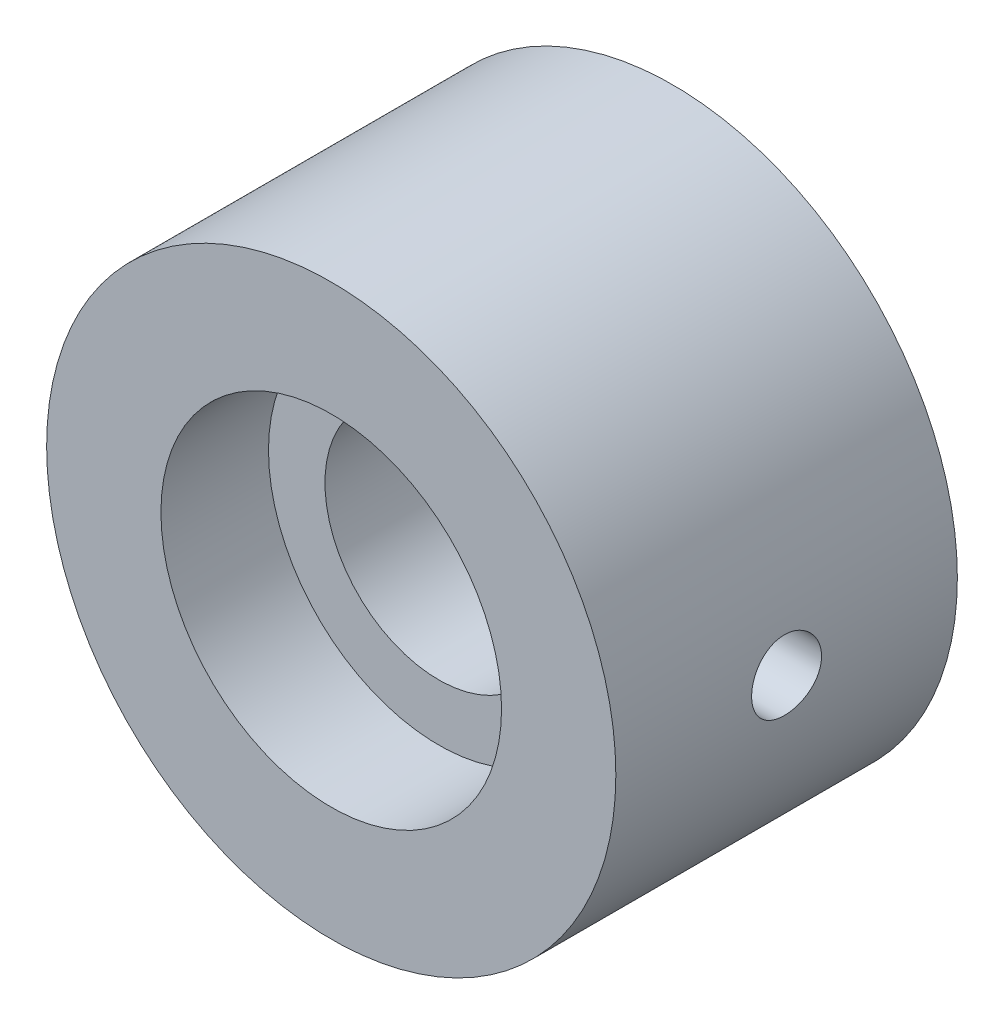
SolidWorks part; units mm, degrees
material "PLA"
ref_plane "Front Plane" through (0, 0, 0) normal (0, 0, 1) x (1, 0, 0)
ref_plane "Top Plane" through (0, 0, 0) normal (0, 1, 0) x (1, 0, 0)
ref_plane "Right Plane" through (0, 0, 0) normal (1, 0, 0) x (0, 0, -1)
sketch "Sketch1" plane through (0, 0, 0) normal (0, 0, 1) x (1, 0, 0)
  circle A0 centre (0, 0) radius 9.5
  circle A1 centre (0, 0) radius 15.875
  circle A2 centre (0, 0) radius 6.35
  dimension "D1" = 19
  dimension "D2" = 31.75
  dimension "D3" = 12.7
extrude "Boss-Extrude1" add sketch "Sketch1" along normal blind 6 contours A1 A0 region at (-15.426, 0, 0)
extrude "Boss-Extrude2" add sketch "Sketch1<3>" against normal blind 13.05 contours A0 A2 | A1 A0 region at (-9.2313, 0, 0) region at (-15.426, 0, 0)
sketch "Sketch1<3>" plane through (0, 0, 0) normal (0, 0, 1) x (1, 0, 0) same geometry as "Sketch1"
sketch "Sketch3" plane through (0, 0, -13.05) normal (0, 0, -1) x (-1, 0, 0)
  line L0 (0, 0) -> (11.5565, 0) construction
  circle A0 centre (0, 12.7) radius 1.95
  circle A1 centre (0, 0) radius 15.875
  circle A2 centre (0, 0) radius 15.875
  circle A3 centre (0, -12.7) radius 1.95
  dimension "D2" = 3.9
  dimension "D3" = 12.7
  dimension "D1" = 0
extrude "Cut-Extrude1" cut sketch "Sketch3" against normal blind 10.16 contours A0 | A3 region at (0, 12.7, -13.05) region at (0, -12.7, -13.05)
ref_plane "Plane1" through (15.875, 0, 0) normal (1, 0, 0) x (0, 0, -1)
sketch "Sketch4" plane through (15.875, 0, 0) normal (1, 0, 0) x (0, 0, -1)
  line L0 (-6, 15.875) -> (-6, -15.875) construction
  line L1 (-6, 15.875) -> (-6, -15.875)
  line L2 (13.05, -15.875) -> (13.05, 15.875) construction
  line L3 (13.05, -15.875) -> (13.05, 15.875)
  line L4 (-6, 0) -> (13.05, 0) construction
  circle A0 centre (3.525, 0) radius 1.95
  dimension "D1" = 3.9
extrude "Cut-Extrude2" cut sketch "Sketch4" against normal up to surface (6.375 mm away) contours L4 A0 | A0 L4 region at (15.875, 0.8276, -3.525) region at (15.875, -0.8276, -3.525) up to face at (9.5, 0, 6)
